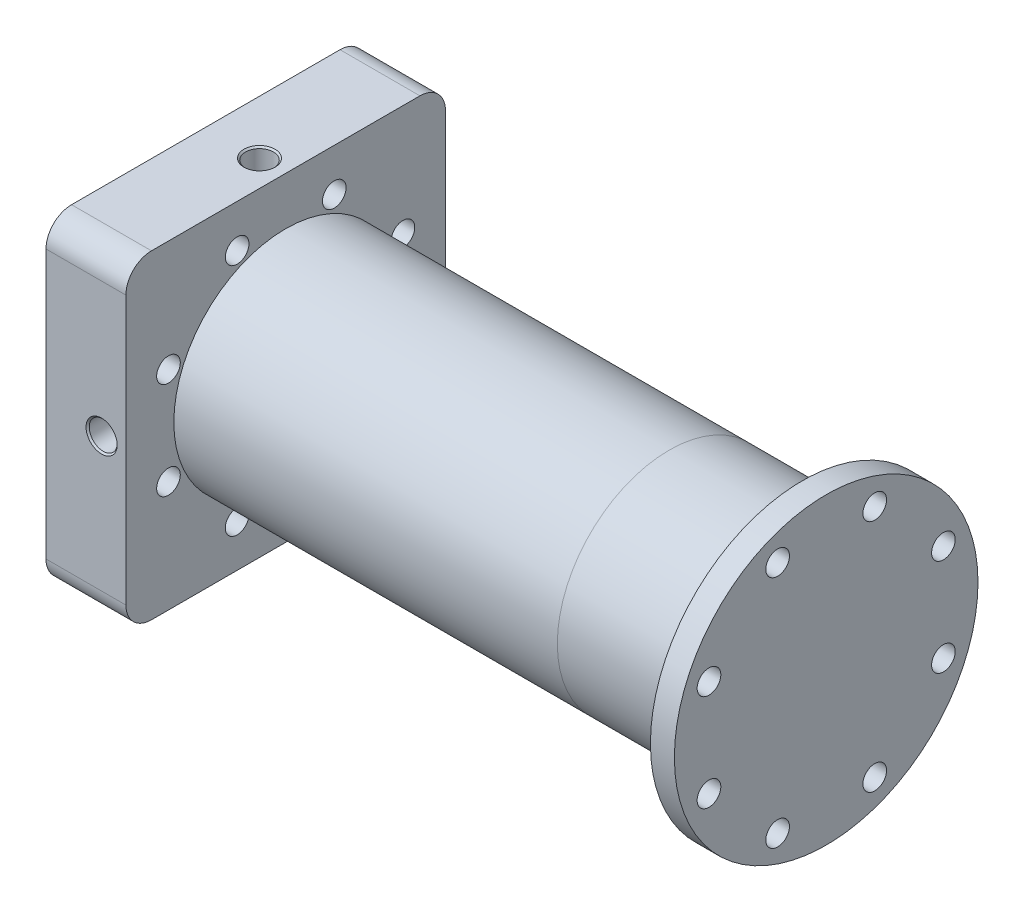
SolidWorks part; units mm, degrees
note: '?' marks a value the reader was unsure of.
other "TC"
other "Injector "
other "Volume "
other "Aft O Ring"
other "Forward O ring"
other "1084N12" parameters "D11"=9.6936, "D1"=8.9273, "D2"=33.6348, "D3"=26.5468, "D4"=23.315, "D5"=33.6348, "D6"=5.8865, "D7"=63.1196, "D8"=7.0953, "D9"=1.4619, "D10"=3.7307, "D12"=6.1926, "D13"=4.361, "D14"=3.81, "D15"=11.3511, "D16"=3.7343, "D17"=3.7343, "D18"=7.0449
ref_plane "Front Plane" through (0, 0, 0) normal (0, 0, 1) x (1, 0, 0)
ref_plane "Top Plane" through (0, 0, 0) normal (0, 1, 0) x (1, 0, 0)
ref_plane "Right Plane" through (0, 0, 0) normal (1, 0, 0) x (0, 0, -1)
sketch "Chamber Revolve" plane through (0, 0, 0) normal (0, 0, 1) x (1, 0, 0)
  line L1 (227.4697, 63.5) -> (227.4697, 26.67)
  line L4 (189.463, 17.801) -> (173.736, 33.528)
  line L5 (173.736, 33.528) -> (0, 33.528)
  line L10 (0, 33.528) -> (0, 42.164)
  line L11 (0, 63.5) -> (10.16, 63.5)
  line L12 (10.16, 63.5) -> (10.16, 47.244)
  line L13 (0, 0) -> (66.3921, 0) construction
  line L15 (191.9165, 17.1436) -> (227.4697, 26.67)
  line L16 (10.16, 47.244) -> (24.13, 47.244)
  line L17 (24.13, 47.244) -> (24.13, 63.5)
  line L18 (24.13, 63.5) -> (227.4697, 63.5)
  line L19 (190.5, 16.764) -> (191.9165, 17.1436) construction
  line L20 (190.5, 16.764) -> (189.463, 17.801) construction
  line L21 (0, 48.2346) -> (3.8608, 48.2346)
  line L22 (3.8608, 48.2346) -> (3.8608, 42.164)
  line L23 (3.8608, 42.164) -> (0, 42.164)
  line L24 (0, 48.2346) -> (0, 63.5)
  arc A0 (189.463, 17.801) -> (191.9165, 17.1436) centre (191.2591, 19.597) ccw
  dimension "D11" = 2.54
  dimension "D2" = 67.056
  dimension "D3" = 53.34
  dimension "D6" = 45
  dimension "D13" = 10.16
  dimension "D8" = 33.528
  dimension "D9" = 36.9697
  dimension "D7" = 13.716
  dimension "D15" = 13.97
  dimension "D5" = 190.5
  dimension "D4" = 15
  dimension "D18" = 6.0706
  dimension "D12" = 127
revolve "Revolve1" add sketch "Chamber Revolve" angle 360 about L13
fillet "Fillet1" radius 1.27 2 edges at (24.13, 0, 47.244) (10.16, 0, 47.244)
sketch "Sketch2" plane through (0, 0, 0) normal (-1, 0, 0) x (0, 0, 1)
  line L0 (0, 0) -> (-24.3004, 58.6664) construction
  line L1 (0, 0) -> (0, 56.6825) construction
  circle A0 centre (-21.7732, 52.565) radius 3.81
  circle A1 centre (0, 0) radius 63.5 construction
  dimension "D2" = 7.62
  dimension "D1" = 6.604
  dimension "D3" = 22.5
extrude "Cut-Extrude1" cut sketch "Sketch2" against normal up to next
pattern_circular "CirPattern1" count 8 over 360 about axis through (0, 0, 0) along (1, 0, 0) of "Cut-Extrude1"
sketch "Sketch4" plane through (0, 0, 0) normal (-1, 0, 0) x (0, 0, 1)
  circle A0 centre (0, 0) radius 63.5
  circle A1 centre (0, 0) radius 63.5 construction
extrude "Boss-Extrude1" add sketch "Sketch4" along normal blind 31.75 separate body
sketch "Sketch5" plane through (0, 0, 0) normal (1, 0, 0) x (0, 0, -1)
  circle A0 centre (21.7732, 52.565) radius 3.81 construction
  circle A1 centre (21.7732, 52.565) radius 3.81
sketch "Sketch11" plane through (-31.75, 0, 0) normal (-1, 0, 0) x (0, 0, 1)
  line L1 (-63.5, -63.5) -> (63.5, -63.5)
  line L2 (-63.5, -63.5) -> (-63.5, 63.5)
  line L3 (-63.5, 63.5) -> (63.5, 63.5)
  line L4 (63.5, -63.5) -> (63.5, 63.5)
  circle A0 centre (0, 0) radius 63.5 construction
  circle A1 centre (0, 0) radius 63.5
  point P6 (0, 63.5)
  point P9 (-63.5, 0)
  circle M18 centre (0, 0) radius 63.5
  dimension "D1" = 127
extrude "Boss-Extrude2" add sketch "Sketch11" against normal up to surface (31.75 mm away) contours L3 L2 L1 M18 | L1 L4 L3 M18 | L4 L3 M18 | L2 L1 M18
sketch "Sketch12" plane through (0, 0, 0) normal (1, 0, 0) x (0, 0, -1)
  circle A0 centre (0, 0) radius 24.13
  dimension "D1" = 48.26
extrude "Cut-Extrude4" cut sketch "Sketch12" against normal blind 16.51
sketch "Sketch13" plane through (0, 0, 63.5) normal (0, 0, 1) x (1, 0, 0)
  line L1 (0, 63.5) -> (0, -63.5) construction
  line L2 (76.835, 0) -> (-76.835, 0) construction
  circle A0 centre (-9.652, 0) radius 1.9685
  dimension "D1" = 3.937
  dimension "D2" = 9.652
extrude "Cut-Extrude5" cut sketch "Sketch13" against normal up to next and the other way through all
sketch "Sketch14" plane through (0, 0, 0) normal (1, 0, 0) x (0, 0, -1)
  line L0 (-63.5, 63.5) -> (63.5, 63.5) construction
  line L1 (-63.5, -63.5) -> (63.5, -63.5) construction
  line L2 (-12.7, 63.5) -> (-63.5, 63.5)
  line L3 (-63.5, 63.5) -> (-63.5, -63.5)
  line L4 (-63.5, -63.5) -> (-12.7, -63.5)
  arc A0 (-12.7, 63.5) -> (-12.7, -63.5) centre (0, 0) ccw
  circle A1 centre (0, 0) radius 63.5 construction
  dimension "D1" = 12.7
chamfer "Chamfer1" distance 4.572 angle 45 1 edges at (0, 0, -24.13)
sketch "Sketch18" plane through (0, 0, 63.5) normal (0, 0, 1) x (1, 0, 0)
  point P0 (-9.652, 0)
hole_wizard "7/16 (0.4375) Diameter Hole1" positions "Sketch18" profile "Sketch20" hole size "7/16" standard "ANSI Inch"
sketch "Sketch20" plane through (-9.652, 0, 63.5) normal (1, 0, 0) x (0, -1, 0)
  line L0 (0, 0) -> (0, 22.3885)
  line L1 (0, 22.3885) -> (5.5562, 19.05)
  line L2 (5.5562, 19.05) -> (5.5562, 0.635)
  line L3 (5.5562, 0.635) -> (6.1912, 0)
  line L5 (6.1912, 0) -> (0, 0)
  line L6 (-5.5562, 0.635) -> (-6.1912, 0) construction
  line L10 (0, 22.3885) -> (-5.5563, 19.05) construction
  line L11 (0, -6.35) -> (0, 107.95) construction
  dimension "Hole Dia." = 11.1125
  dimension "Hole Depth" = 19.05
  dimension "Near C'Sink Dia." = 12.3825
  dimension "Near C'Sink Angle" = 90
  dimension "Drill Angle" = 118
mirror "Mirror1" about plane through (0, 0, 0) normal (0, 0, 1) of "7/16 (0.4375) Diameter Hole1", "Cut-Extrude5"
sketch "Sketch21" plane through (0, 0, 0) normal (0, 1, 0) x (1, 0, 0)
  line L0 (0, 33.528) -> (173.736, 33.528)
  line L1 (0, 42.164) -> (0, -42.164) construction
  line L2 (0, 33.528) -> (0, -33.528) construction
  line L3 (173.736, -33.528) -> (173.736, 33.528) construction
  line L4 (173.736, 33.528) -> (189.463, 17.801)
  line L5 (189.463, -17.801) -> (189.463, 17.801) construction
  line L6 (189.463, 17.801) -> (189.463, 0)
  line L10 (0, 0) -> (0, 33.528)
  line L11 (0, 0) -> (189.463, 0)
  line L12 (189.463, 0) -> (214.4295, 0) construction
revolve "Revolve2" add sketch "Sketch21" angle 360 about L12
fillet "Fillet2" radius 0.889 2 edges at (3.8608, 0, 42.164) (3.8608, 0, 48.2346)
sketch "Sketch22" plane through (-31.75, 0, 0) normal (-1, 0, 0) x (0, 0, 1)
  point P0 (0, -33.02)
  dimension "D1" = 33.02
hole_wizard "Ø6.7 (6.7) Diameter Hole1" positions "Sketch22" profile "Sketch23" hole size "Ø6.7" standard "ANSI Metric"
sketch "Sketch23" plane through (-31.75, -33.02, 0) normal (0, 1, 0) x (0, 0, 1)
  line L0 (0, 0) -> (0, 15.2209)
  line L1 (0, 15.2209) -> (3.35, 13.208)
  line L2 (3.35, 13.208) -> (3.35, 0.4)
  line L3 (3.35, 0.4) -> (3.75, 0)
  line L5 (3.75, 0) -> (0, 0)
  line L6 (-3.35, 0.4) -> (-3.75, 0) construction
  line L10 (0, 15.2209) -> (-3.35, 13.208) construction
  line L11 (0, -6.35) -> (0, 107.95) construction
  dimension "Hole Dia." = 6.7
  dimension "Hole Depth" = 13.208
  dimension "Near C'Sink Dia." = 7.5
  dimension "Near C'Sink Angle" = 90
  dimension "Drill Angle" = 118
mirror "Mirror2" about plane through (0, 0, 0) normal (0, 1, 0) of "Ø6.7 (6.7) Diameter Hole1"
sketch "Sketch24" plane through (0, 0, 0) normal (0, 1, 0) x (1, 0, 0)
  line L0 (-31.75, 63.5) -> (-31.75, -63.5) construction
  line L1 (-31.75, 7.1374) -> (-30.9581, 5.7658)
  line L2 (-30.9581, 5.7658) -> (-29.845, 5.7658)
  line L3 (-29.4858, 5.617) -> (-28.7329, 4.8641)
  line L4 (-28.7329, 4.8641) -> (-16.51, 4.8641)
  line L5 (-16.51, -24.13) -> (-16.51, 24.13) construction
  line L6 (-16.51, 4.8641) -> (-16.51, 0)
  line L7 (-16.51, 0) -> (-31.75, 0)
  line L8 (-31.75, 0) -> (-31.75, 7.1374)
  line L9 (-29.845, 5.7658) -> (-29.6346, 5.7658) construction
  line L10 (-29.6346, 5.7658) -> (-29.4858, 5.617) construction
  line L11 (-31.75, 0) -> (-56.3457, 0) construction
  arc A0 (-29.845, 5.7658) -> (-29.4858, 5.617) centre (-29.845, 5.2578) cw
  dimension "D2" = 0.508
  dimension "D1" = 60
  dimension "D3" = 4.8641
  dimension "D4" = 7.1374
  dimension "D5" = 5.7658
  dimension "D6" = 1.905
  dimension "D7" = 45
  dimension "D8" = 15.24
ref_axis "Axis1" through (227.4697, 0, 0) along (-1, 0, 0)
revolve "Cut-Revolve1" cut sketch "Sketch24" angle 360 about axis through (227.4697, 0, 0) along (-1, 0, 0)
fillet "Fillet3" radius 0.508 1 edges at (-30.9581, 0, -5.7658)
sketch "Sketch25" plane through (0, 0, 0) normal (0, 0, 1) x (1, 0, 0)
  line L0 (0, -63.5) -> (-31.75, -63.5) construction
  line L1 (0, -63.5) -> (-31.75, -63.5) construction
  line L2 (-4.318, -63.5) -> (-5.4699, -62.8349)
  line L3 (-5.588, -62.6304) -> (-5.588, -61.468)
  line L4 (-11.43, -26.67) -> (-9.398, -26.67)
  line L5 (-5.7368, -61.1088) -> (-6.604, -60.2416)
  line L6 (-6.604, -60.2416) -> (-6.604, -46.8376)
  line L7 (-11.43, -63.5) -> (-11.43, -26.67)
  line L8 (-16.51, -24.13) -> (-16.51, 24.13) construction
  line L9 (-6.604, -46.8376) -> (-9.398, -45.1588)
  line L10 (-9.398, -45.1588) -> (-9.398, -26.67)
  line L11 (-16.51, -24.13) -> (-16.51, 24.13) construction
  line L12 (-11.43, -63.5) -> (-4.318, -63.5)
  line L13 (-11.43, -63.5) -> (-11.43, -73.7659) construction
  arc A1 (-5.588, -61.468) -> (-5.7368, -61.1088) centre (-6.096, -61.468) ccw
  arc A2 (-5.4699, -62.8349) -> (-5.588, -62.6304) centre (-5.3518, -62.6304) cw
  dimension "D4" = 0.2362
  dimension "D6" = 0.508
  dimension "D1" = 7.112
  dimension "D2" = 5.08
  dimension "D3" = 60
  dimension "D5" = 5.842
  dimension "D7" = 45
  dimension "D8" = 2.032
  dimension "D9" = 4.826
  dimension "D10" = 16.6624
  dimension "D11" = 59
  dimension "D12" = 2.032
  dimension "D13" = 2.54
sketch "Sketch29" plane through (0, -63.5, 0) normal (0, -1, 0) x (-1, 0, 0)
  line L0 (0, -63.5) -> (0, 63.5) construction
  point P0 (10.414, 0)
  dimension "D1" = 10.414
hole_wizard "7/16 (0.4375) Diameter Hole2" positions "Sketch29" profile "Sketch30" hole size "7/16" standard "ANSI Inch"
sketch "Sketch30" plane through (-10.414, -63.5, 0) normal (1, 0, 0) x (0, 0, -1)
  line L0 (0, 0) -> (0, 22.3885)
  line L1 (0, 22.3885) -> (5.5562, 19.05)
  line L2 (5.5562, 19.05) -> (5.5562, 0.635)
  line L3 (5.5562, 0.635) -> (6.1913, 0)
  line L5 (6.1913, 0) -> (0, 0)
  line L6 (-5.5562, 0.635) -> (-6.1913, 0) construction
  line L10 (0, 22.3885) -> (-5.5563, 19.05) construction
  line L11 (0, -6.35) -> (0, 107.95) construction
  dimension "Hole Dia." = 11.1125
  dimension "Hole Depth" = 19.05
  dimension "Near C'Sink Dia." = 12.3825
  dimension "Near C'Sink Angle" = 90
  dimension "Drill Angle" = 118
sketch "Sketch31" plane through (0, -63.5, 0) normal (0, -1, 0) x (1, 0, 0)
  circle A0 centre (-10.414, 0) radius 1.5875
  dimension "D1" = 3.175
extrude "Cut-Extrude9" cut sketch "Sketch31" against normal up to surface (39.4223 mm away)
mirror "Mirror3" about plane through (0, 0, 0) normal (0, 1, 0) of "Cut-Extrude9", "7/16 (0.4375) Diameter Hole2"
delete or keep bodies "Body-Delete/Keep 1" type delete bodies bodies 103
sketch "Sketch37" plane through (0, 0, 0) normal (1, 0, 0) x (0, 0, -1)
  line L0 (-63.5, -63.5) -> (63.5, -63.5) construction
  line L1 (-63.5, 63.5) -> (63.5, 63.5) construction
  line L2 (63.5, 63.5) -> (63.5, -63.5) construction
  line L3 (-63.5, 63.5) -> (-63.5, -63.5) construction
  line L4 (-63.5, -63.5) -> (63.5, -63.5)
  line L5 (-63.5, 63.5) -> (63.5, 63.5)
  line L6 (63.5, 63.5) -> (63.5, -63.5)
  line L7 (-63.5, 63.5) -> (-63.5, -63.5)
  circle A0 centre (0, 0) radius 43.688
  dimension "D1" = 87.376
sketch "Sketch32" plane through (0, 0, 0) normal (1, 0, 0) x (0, 0, -1)
  circle A0 centre (0, 0) radius 44.45
  circle A1 centre (0, 0) radius 69.85
  dimension "D1" = 88.9
  dimension "D2" = 139.7
sketch "Sketch33" plane through (0, 0, 0) normal (1, 0, 0) x (0, 0, -1)
  circle A0 centre (0, 0) radius 34.925
  circle A1 centre (0, 0) radius 44.45
  dimension "D1" = 69.85
  dimension "D2" = 88.9
extrude "Boss-Extrude4" add sketch "Sketch33" along normal blind 152.4 separate body
sketch "Sketch34" plane through (0, 0, 0) normal (0, 0, 1) x (1, 0, 0)
  line L2 (152.4, 44.45) -> (152.4, 34.925)
  line L6 (152.4, 34.925) -> (165.1165, 16.764)
  line L7 (165.1165, 16.764) -> (202.0862, 26.67)
  line L8 (202.0862, 26.67) -> (202.0862, 44.45)
  line L9 (202.0862, 44.45) -> (152.4, 44.45)
  line L10 (154.0002, 0) -> (250.6574, 0) construction
  line L11 (152.4, -34.925) -> (152.4, 34.925) construction
  line L12 (152.4, -44.45) -> (152.4, 44.45) construction
  line L13 (152.4, -34.925) -> (152.4, 34.925) construction
  line L14 (152.4, -44.45) -> (152.4, 44.45) construction
  dimension "D1" = 33.528
  dimension "D2" = 53.34
  dimension "D3" = 15
  dimension "D7" = 55
ref_axis "Axis2" through (152.4, 0, 0) along (-1, 0, 0)
revolve "Revolve3" add sketch "Sketch34" angle 360 about axis through (152.4, 0, 0) along (-1, 0, 0)
fillet "Fillet5" radius 1.27 1 edges at (165.1165, 0, -16.764)
sketch "Sketch35" plane through (0, 0, 0) normal (1, 0, 0) x (0, 0, -1)
  line L0 (0, 0) -> (0, 81.6848) construction
  line L1 (0, 0) -> (18.5655, 44.8211) construction
  line L2 (17.0103, 41.0664) -> (18.5655, 44.8211) construction
  circle A0 centre (18.5655, 44.8211) radius 4.064
  circle A1 centre (0, 0) radius 44.45 construction
  dimension "D1" = 8.128
  dimension "D2" = 22.5
  dimension "D3" = 4.064
fillet "Fillet6" radius 10.16 4 edges at (-15.875, -63.5, 63.5) (-15.875, -63.5, -63.5) (-15.875, 63.5, -63.5) (-15.875, 63.5, 63.5)
sketch "Sketch39" plane through (202.0862, 0, 0) normal (1, 0, 0) x (0, 0, -1)
  circle A0 centre (0, 0) radius 36.195
  circle A1 centre (0, 0) radius 60.325
  dimension "D1" = 72.39
  dimension "D2" = 120.65
extrude "Boss-Extrude6" add sketch "Sketch39" along normal blind 9.525 separate body
sketch "Sketch40" plane through (202.0862, 0, 0) normal (-1, 0, 0) x (0, 0, 1)
  line L0 (0, 0) -> (0, 54.3419) construction
  line L1 (0, 0) -> (-19.2945, 46.5811) construction
  circle A0 centre (-19.2945, 46.5811) radius 4.699
  circle A2 centre (0, 0) radius 44.45 construction
  circle A3 centre (0, 0) radius 44.45 construction
  point P5 (-17.0103, 41.0664)
  point P8 (-17.4963, 42.2398)
  dimension "D2" = 9.398
  dimension "D3" = 1.27
  dimension "D1" = 22.5
extrude "Cut-Extrude13" cut sketch "Sketch40" along normal through all both and the other way through all
pattern_circular "CirPattern3" count 8 over 360 about axis through (0, 0, 0) along (1, 0, 0) of "Cut-Extrude13"
sketch "Sketch41" plane through (0, 0, 0) normal (0, 0, 1) x (1, 0, 0)
  line L0 (0, 37.338) -> (-2.1844, 37.338)
  line L1 (0, 53.34) -> (0, -53.34) construction
  line L2 (-2.6416, 37.7952) -> (-2.6416, 40.9702)
  line L3 (-2.1844, 41.4274) -> (0, 41.4274)
  line L4 (0, 0) -> (38.5106, 0) construction
  line L5 (-2.6416, 41.4274) -> (-2.1844, 41.4274) construction
  line L6 (-2.6416, 40.9702) -> (-2.6416, 41.4274) construction
  line L7 (-2.6416, 37.338) -> (-2.6416, 37.7952) construction
  line L8 (-2.1844, 37.338) -> (-2.6416, 37.338) construction
  line L9 (0, 37.338) -> (0, 41.4274)
  arc A0 (-2.1844, 41.4274) -> (-2.6416, 40.9702) centre (-2.1844, 40.9702) ccw
  arc A1 (-2.6416, 37.7952) -> (-2.1844, 37.338) centre (-2.1844, 37.7952) ccw
  dimension "D4" = 0.4572
  dimension "D1" = 4.0894
  dimension "D2" = 2.6416
  dimension "D3" = 41.4274
revolve "Cut-Revolve2" cut sketch "Sketch41" angle 360 about L4
sketch "Sketch43" plane through (0, 0, 0) normal (0, 0, 1) x (1, 0, 0)
  circle A0 centre (-1.1621, 39.5944) radius 1.3347
sketch "Sketch44" plane through (0, 0, 0) normal (0, 0, 1) x (1, 0, 0)
  line L0 (-2.6416, -40.9702) -> (-2.6416, 40.9702) construction
  line L1 (-2.6416, -40.9702) -> (-2.6416, 40.9702) construction
  line L2 (-2.1844, 41.4274) -> (-2.1844, -41.4274) construction
  line L3 (-2.1844, 41.4274) -> (-2.1844, -41.4274) construction
  line L4 (-2.1844, 41.4274) -> (-6.4254, 41.4274) construction
  circle A0 centre (-0.8763, 39.6621) radius 1.7653
  dimension "D1" = 3.5306
revolve "Revolve4" add sketch "Sketch44" angle 360 about L4
ref_plane "Plane1" through (76.2, 0, 0) normal (1, 0, 0) x (0, 0, -1)
sketch "Sketch45" plane through (0, 0, 0) normal (0, 0, 1) x (1, 0, 0)
  line L0 (152.4, 41.4274) -> (154.5336, 41.4274)
  line L1 (152.4, -44.45) -> (152.4, 44.45) construction
  line L2 (155.0416, 40.9194) -> (155.0416, 37.846)
  line L3 (154.5336, 37.338) -> (152.4, 37.338)
  line L4 (152.4, 41.4274) -> (152.4, 37.338)
  line L5 (152.4, 39.3827) -> (151.151, 39.3827) construction
  line L6 (154.5336, 41.4274) -> (155.0416, 41.4274) construction
  line L7 (155.0416, 41.4274) -> (155.0416, 40.9194) construction
  line L8 (155.0416, 37.846) -> (155.0416, 37.338) construction
  line L9 (155.0416, 37.338) -> (154.5336, 37.338) construction
  arc A0 (154.5336, 41.4274) -> (155.0416, 40.9194) centre (154.5336, 40.9194) cw
  arc A1 (154.5336, 37.338) -> (155.0416, 37.846) centre (154.5336, 37.846) ccw
  dimension "D3" = 41.4274
  dimension "D4" = 0.508
  dimension "D1" = 2.6416
  dimension "D2" = 4.0894
revolve "Cut-Revolve3" cut sketch "Sketch45" angle 360 about L4
mirror "Mirror9" about plane through (76.2, 0, 0) normal (1, 0, 0) of bodies 157
ref_axis "Axis3" through (202.0862, 46.5811, -19.2945) along (1, 0, 0)?
delete or keep bodies "Body-Delete/Keep 2" bodies 151
sketch "Sketch46" plane through (202.0862, 0, 0) normal (1, 0, 0) x (0, 0, -1)
  circle A0 centre (0, 0) radius 38.1
  dimension "D1" = 76.2
extrude "Boss-Extrude7" add sketch "Sketch46" along normal blind 3.175 separate body
sketch "Sketch47" plane through (205.2612, 0, 0) normal (1, 0, 0) x (0, 0, -1)
  circle A0 centre (0, 0) radius 60.325
  circle A1 centre (-46.5811, 19.2945) radius 4.699 construction
  circle A2 centre (-46.5811, -19.2945) radius 4.699 construction
  circle A3 centre (-19.2945, -46.5811) radius 4.699 construction
  circle A4 centre (19.2945, -46.5811) radius 4.699 construction
  circle A5 centre (46.5811, -19.2945) radius 4.699 construction
  circle A6 centre (46.5811, 19.2945) radius 4.699 construction
  circle A7 centre (19.2945, 46.5811) radius 4.699 construction
  circle A8 centre (-19.2945, 46.5811) radius 4.699 construction
  circle A9 centre (-46.5811, 19.2945) radius 4.699
  circle A10 centre (-46.5811, -19.2945) radius 4.699
  circle A11 centre (-19.2945, -46.5811) radius 4.699
  circle A12 centre (19.2945, -46.5811) radius 4.699
  circle A13 centre (46.5811, -19.2945) radius 4.699
  circle A14 centre (46.5811, 19.2945) radius 4.699
  circle A15 centre (19.2945, 46.5811) radius 4.699
  circle A16 centre (-19.2945, 46.5811) radius 4.699
  dimension "D1" = 120.65
extrude "Boss-Extrude8" add sketch "Sketch47" along normal blind 9.525 separate body
equation "\"Throat Diameter\"= 1.32"
equation "\"Exit Diameter\"= 2.1"
equation "\"D3@Chamber Revolve\"=\"Exit Diameter\""
equation "\"D8@Chamber Revolve\"=\"Throat Diameter\""
equation "\"Injector Ox D\"= 3mm"
equation "\"Injector Fuel D\"= 2mm"
equation "\"Chamber Diameter\"= \"Chamber Throat D Ratio\" * ( \"Throat Diameter\" )"
equation "\"Chamber Throat D Ratio\"= 2"
equation "\"L*\"= 30"
equation "\"Lc\"= \"L*\" / ( \"Chamber Throat D Ratio\" ^ 2 )"
equation "\"T_min\"= 2 * .17"
equation "\"D2@Chamber Revolve\"=\"Chamber Diameter\""
equation "\"D7@Chamber Revolve\"=\"T_min\" +.2"
equation "\"D5@Chamber Revolve\"=\"Lc\""
equation "\"No Flange Holes\"= 8"
equation "\"D1@CirPattern1\"=\"No Flange Holes\""
equation "\"D16@Chamber Revolve\"=\"T_min\""
equation "\"D1@Sketch34\"=\"Throat Diameter\""
equation "\"D2@Sketch34\"=\"Exit Diameter\""
equation "\"D3@Sketch35\"=\"D1@Sketch35\"/2"
equation "\"O ring Groove Width\"= .161"
equation "\"Oring Groove Depth\"= .104"
equation "\"O ring Od\"=3.262"
equation "\"D3@Sketch41\"=\"O ring Od\"/2"
equation "\"D1@Sketch41\"=\"O ring Groove Width\""
equation "\"D2@Sketch41\"=\"Oring Groove Depth\""
equation "\"Corner Rad O ring\"= .018"
equation "\"D4@Sketch41\"=\"Corner Rad O ring\""
equation "\"D1@Sketch45\"=\"Oring Groove Depth\""
equation "\"D2@Sketch45\"=\"O ring Groove Width\""
equation "\"D3@Sketch45\"=\"O ring Od\"/2"
